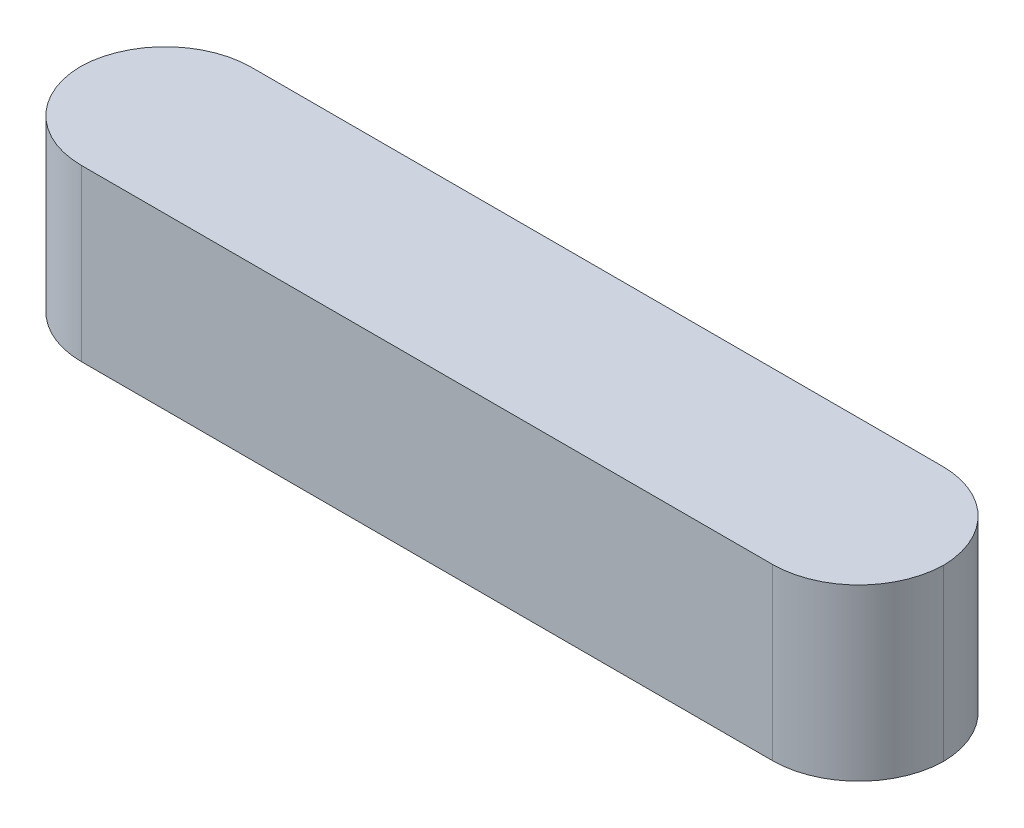
SolidWorks part; units mm, degrees
ref_plane "Front Plane" through (0, 0, 0) normal (0, 0, 1) x (1, 0, 0)
ref_plane "Top Plane" through (0, 0, 0) normal (0, 1, 0) x (1, 0, 0)
ref_plane "Right Plane" through (0, 0, 0) normal (1, 0, 0) x (0, 0, -1)
sketch "Sketch1" plane through (0, 0, 0) normal (0, 1, 0) x (1, 0, 0)
  line L1 (0, 0) -> (25.4, 0)
  line L2 (0, 0) -> (0, -5)
  line L3 (0, -5) -> (25.4, -5)
  line L4 (25.4, 0) -> (25.4, -5)
  dimension "D1" = 25.4
  dimension "D2" = 5
extrude "Boss-Extrude1" add sketch "Sketch1" along normal blind 5
fillet "Fillet1" radius 2.54 4 edges at (0, 2.5, 5) (0, 2.5, 0) (25.4, 2.5, 0) (25.4, 2.5, 5)
